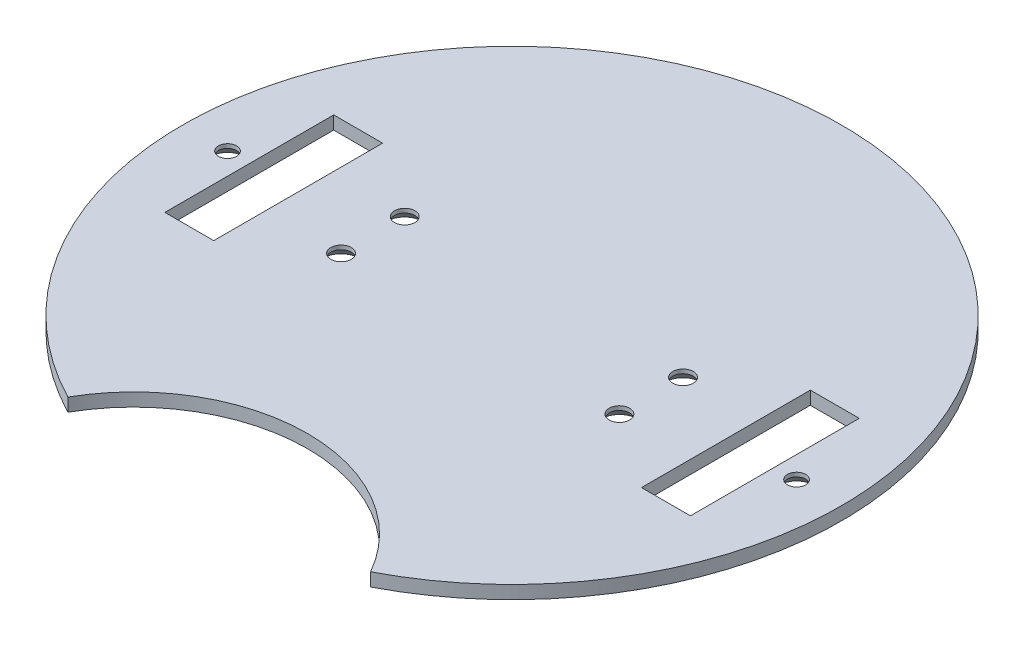
SolidWorks part; units mm, degrees
ref_plane "Front Plane" through (0, 0, 0) normal (0, 0, 1) x (1, 0, 0)
ref_plane "Top Plane" through (0, 0, 0) normal (0, 1, 0) x (1, 0, 0)
ref_plane "Right Plane" through (0, 0, 0) normal (1, 0, 0) x (0, 0, -1)
sketch "Sketch1" plane through (0, 0, 0) normal (0, 1, 0) x (1, 0, 0)
  line L0 (0, -83.2398) -> (-33.2911, -64.4046) construction
  line L1 (0, -83.2398) -> (0, 0) construction
  arc A0 (33.2911, -64.4046) -> (-33.2911, -64.4046) centre (0, 0) ccw
  arc A1 (33.2911, -64.4046) -> (-33.2911, -64.4046) centre (0, -83.2398) ccw
  dimension "D1" = 145
  dimension "D2" = 76.5
  dimension "D3" = 60.5
extrude "Boss-Extrude1" add sketch "Sketch1" along normal blind 2.9
sketch "solenoid placement" plane through (0, 2.9, 0) normal (0, 1, 0) x (1, 0, 0)
  line L0 (0, 0) -> (0, -36) construction
  line L1 (0, -36) -> (0, -44.9898) construction
  line L2 (-19, -36) -> (19, -36)
  line L3 (-19, -36) -> (-19, 28.4)
  line L4 (-19, 28.4) -> (19, 28.4)
  line L5 (19, -36) -> (19, 28.4)
  circle A1 centre (0, 0) radius 72.5 construction
  arc A2 (33.2911, -64.4046) -> (-33.2911, -64.4046) centre (0, 0) ccw construction
  arc A3 (33.2911, -64.4046) -> (-33.2911, -64.4046) centre (0, -83.2398) ccw construction
  dimension "D1" = 64.4
  dimension "D2" = 36
  dimension "D4" = 38
sketch "Sketch2" plane through (0, 2.9, 0) normal (0, 1, 0) x (1, 0, 0)
  line L1 (-57.5, 18.2695) -> (-47.34, 18.2695) construction
  line L2 (-57.5, 18.2695) -> (-57.5, -18.2695) construction
  line L3 (-57.5, -18.2695) -> (-47.34, -18.2695) construction
  line L4 (-47.34, 18.2695) -> (-47.34, -18.2695) construction
  line L8 (-57.8, -18.5695) -> (-47.04, -18.5695)
  line L9 (-47.04, 18.5695) -> (-47.04, -18.5695)
  line L10 (-57.8, 18.5695) -> (-47.04, 18.5695)
  line L11 (-57.8, 18.5695) -> (-57.8, -18.5695)
  line L12 (0, 0) -> (0, 72.5) construction
  line L13 (47.34, 18.2695) -> (47.34, -18.2695) construction
  line L14 (57.5, -18.2695) -> (47.34, -18.2695) construction
  line L15 (57.5, 18.2695) -> (57.5, -18.2695) construction
  line L16 (57.5, 18.2695) -> (47.34, 18.2695) construction
  line L17 (57.8, 18.5695) -> (57.8, -18.5695)
  line L18 (57.8, 18.5695) -> (47.04, 18.5695)
  line L19 (47.04, 18.5695) -> (47.04, -18.5695)
  line L20 (57.8, -18.5695) -> (47.04, -18.5695)
  arc A0 (33.2911, -64.4046) -> (-33.2911, -64.4046) centre (0, 0) ccw construction
extrude "Cut-Extrude1" cut sketch "Sketch2" against normal through all
sketch "Sketch3" plane through (0, 0, 0) normal (0, -1, 0) x (1, 0, 0)
  line L0 (0, 0) -> (0, -72.5) construction
  circle A0 centre (-62.58, 0) radius 2
  circle A1 centre (-30.61, 7) radius 2.25
  circle A2 centre (-30.61, -7) radius 2.25
  arc A3 (-33.2911, 64.4046) -> (33.2911, 64.4046) centre (0, 0) ccw construction
  circle A4 centre (30.61, -7) radius 2.25
  circle A5 centre (30.61, 7) radius 2.25
  circle A6 centre (62.58, 0) radius 2
  dimension "D1" = 4
  dimension "D2" = 4.5
extrude "Cut-Extrude2" cut sketch "Sketch3" against normal through all
chamfer "Chamfer1" distance 2 angle 41 6 edges at (-30.61, 0, -9.25) (-30.61, 0, 4.75) (-62.58, 0, -2) (62.58, 0, 2) (30.61, 0, 9.25) (30.61, 0, -4.75) first distance on face at (-30.61, 2.9, -9.25) first distance on face at (-30.61, 2.9, 4.75) first distance on face at (-62.58, 2.9, -2) first distance on face at (62.58, 2.9, 2) first distance on face at (30.61, 2.9, 9.25) first distance on face at (30.61, 2.9, -4.75)
equation "\"smallPulleyTeeth\"= 15"
equation "\"largePulleyTeeth\"= 40"
equation "\"eighthThick\"= 2.9mm"
equation "\"sixteenthThick\"= 1.7mm"
equation "\"quarterThick\"=5.9mm"
equation "\"OD\"= 145mm"
equation "\"puckAngle\"= 60.5deg"
equation "\"D1@Sketch1\"=\"OD\""
equation "\"puckDiam\"= 76.5mm"
equation "\"D2@Sketch1\"=\"puckDiam\""
equation "\"D3@Sketch1\"=\"puckAngle\""
equation "\"D1@Boss-Extrude1\"=\"eighthThick\""
equation "\"axlePress\"= 5.9mm"
equation "\"press\"= 0.2mm"
equation "\"wheelClear\"= 0.3mm"
equation "\"D1@Sketch2\"=\"wheelClear\""
equation "\"10-32clear\"= 4.5mm"
equation "\"6-32clear\"= 3.3mm"
equation "\"8-32clear\"= 4.0mm"
equation "\"wheelHeight\"= 24mm"
equation "\"D1@Sketch3\"=\"8-32clear\""
equation "\"D2@Sketch3\"=\"10-32clear\""
